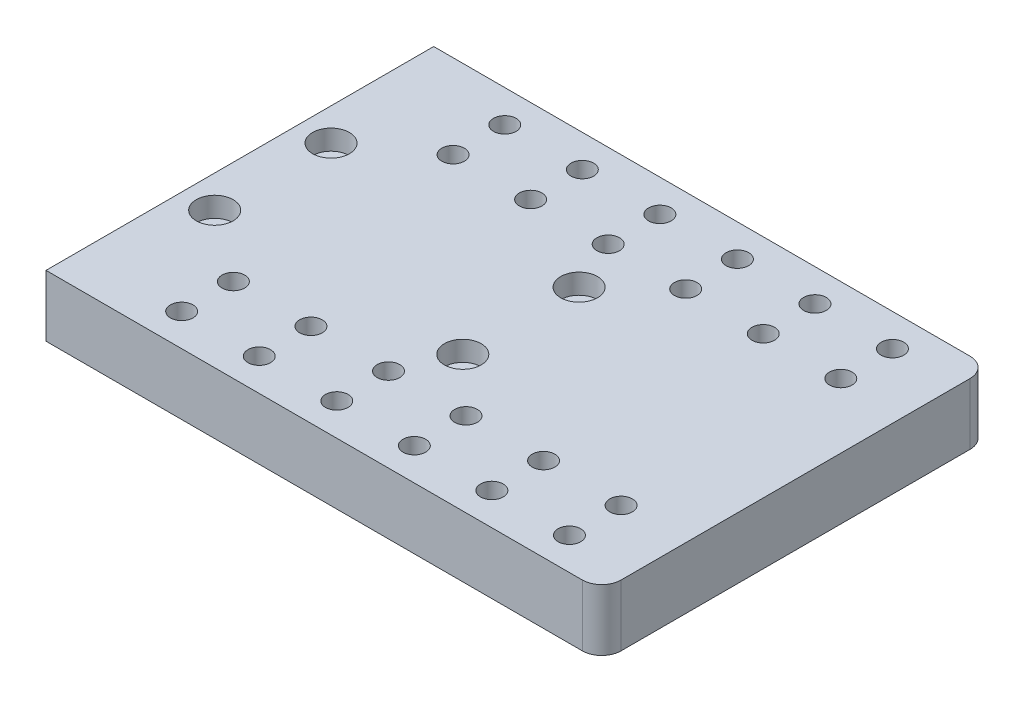
SolidWorks part; units mm, degrees
ref_plane "前视基准面" through (0, 0, 0) normal (0, 0, 1) x (1, 0, 0)
ref_plane "上视基准面" through (0, 0, 0) normal (0, 1, 0) x (1, 0, 0)
ref_plane "右视基准面" through (0, 0, 0) normal (1, 0, 0) x (0, 0, -1)
sketch "草图1" plane through (0, 0, 0) normal (0, 1, 0) x (1, 0, 0)
  line L1 (-43, 30) -> (43, 30)
  line L2 (-43, 30) -> (-43, -30)
  line L3 (-43, -30) -> (43, -30)
  line L4 (43, 30) -> (43, -30)
  line L5 (-43, 30) -> (43, -30) construction
  line L6 (-43, -30) -> (43, 30) construction
  point P0 (0, 0)
  dimension "D1" = 60
  dimension "D2" = 86
extrude "凸台-拉伸1" add sketch "草图1" along normal blind 9.5
fillet "圆角1" radius 3 2 edges at (43, 4.75, -30) (43, 4.75, 30)
sketch "草图2" plane through (0, 9.5, 0) normal (0, 1, 0) x (1, 0, 0)
  circle A0 centre (-38, -8.8898) radius 1.25
  circle A1 centre (-38, 9.1102) radius 1.25
  circle A2 centre (0.5, 9) radius 1.25
  circle A3 centre (0.5, -9) radius 1.25
  dimension "D1" = 2.5
extrude "切除-拉伸1" cut sketch "草图2" against normal through all
sketch "草图3" plane through (0, 9.5, 0) normal (0, 1, 0) x (1, 0, 0)
  circle A0 centre (-38, -8.8898) radius 2.85
  circle A1 centre (-38, 9.1102) radius 2.85
  circle A2 centre (0.5, -9) radius 2.85
  circle A3 centre (0.5, 9) radius 2.85
  dimension "D1" = 5.7
extrude "切除-拉伸2" cut sketch "草图3" against normal blind 3.1
sketch "草图4" plane through (0, 9.5, 0) normal (0, 1, 0) x (1, 0, 0)
  line L0 (-43, -30) -> (40, -30) construction
  line L1 (40, 30) -> (-43, 30) construction
  line L2 (43, -27) -> (43, 27) construction
  circle A0 centre (-27, -25) radius 1.75
  circle A1 centre (-27, 25) radius 1.75
  circle A2 centre (-27, -17) radius 1.75
  circle A3 centre (-27, 17) radius 1.75
  dimension "D1" = 3.5
  dimension "D2" = 5
  dimension "D3" = 5
  dimension "D4" = 70
  dimension "D5" = 8
  dimension "D6" = 8
  dimension "D9" = 70
extrude "切除-拉伸3" cut sketch "草图4" against normal through all
pattern_linear "阵列(线性)1" count 6 spacing 12 along (1, 0, 0) of "切除-拉伸3"
